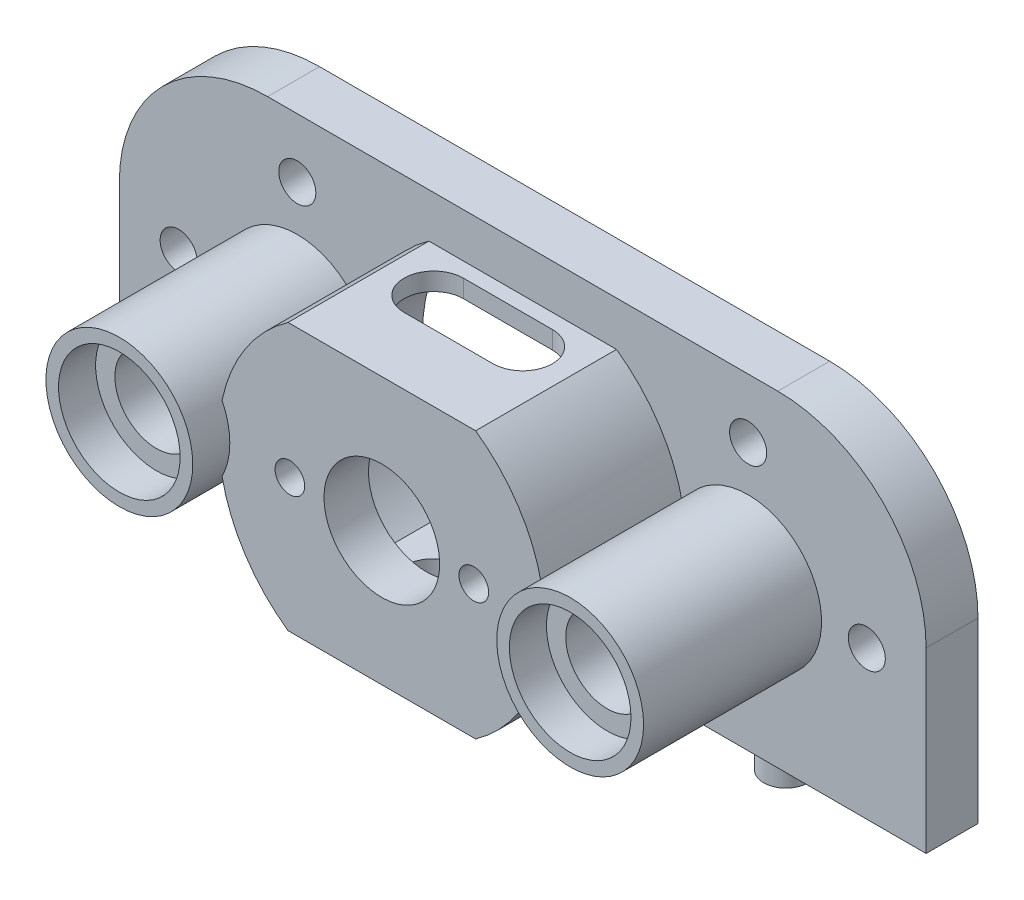
SolidWorks part; units mm, degrees
ref_plane "前视基准面" through (0, 0, 0) normal (0, 0, 1) x (1, 0, 0)
ref_plane "上视基准面" through (0, 0, 0) normal (0, 1, 0) x (1, 0, 0)
ref_plane "右视基准面" through (0, 0, 0) normal (1, 0, 0) x (0, 0, -1)
other "Configuration Table"
sketch "草图2" plane through (0, 0, 0) normal (0, 0, 1) x (1, 0, 0)
  line L0 (0, 0) -> (11.5094, 0) construction
  line L1 (0, 0) -> (0, 7.1412) construction
  line L2 (15.2, 0) -> (-15.2, 0) construction
  line L3 (15.2, -20) -> (-15.2, -20)
  line L4 (15.2, 20) -> (-15.2, 20)
  circle A0 centre (0, 0) radius 3.9
  circle A1 centre (-15.2, 0) radius 2.8
  circle A2 centre (-15.2, 0) radius 4.1
  arc A3 (15.2, -20) -> (15.2, 20) centre (15.2, 0) ccw
  arc A4 (-15.2, 20) -> (-15.2, -20) centre (-15.2, 0) ccw
  circle A5 centre (15.2, 0) radius 2.8
  circle A6 centre (15.2, 0) radius 4.1
  circle A7 centre (-6.2, 0) radius 1
  circle A9 centre (6.2, 0) radius 1
  circle A11 centre (-15.2, 8) radius 1.25
  circle A12 centre (-23.2, 0) radius 1.25
  circle A15 centre (23.2, 0) radius 1.25
  circle A16 centre (15.2, 8) radius 1.25
  point P11 (0, 0)
  dimension "D1" = 7.8
  dimension "D2" = 5.6
  dimension "D4" = 8.2
  dimension "D5" = 20
  dimension "D6" = 2
  dimension "D10" = 2.5
  dimension "D12" = 2.5
  dimension "D3" = 15.2
  dimension "D7" = 6.2
  dimension "D11" = 8
  dimension "D13" = 8
extrude "凸台-拉伸1" add sketch "草图2" along normal blind 3.5 contours L4 A4 L3 A3 A15 A6 A2 A0 A7 A9 A11 A12 A16 region at (0, -19.1903, 0)
extrude "凸台-拉伸2" add sketch "草图2<4>" along normal blind 1 contours A2 A1 | A6 A5 region at (-19.184, 0, 0) region at (11.216, 0, 0)
sketch "草图2<4>" plane through (0, 0, 0) normal (0, 0, 1) x (1, 0, 0) same geometry as "草图2"
sketch "草图3" plane through (0, 0, 3.5) normal (0, 0, 1) x (1, 0, 0)
  line L3 (15.2, -20) -> (-15.2, -20) construction
  line L4 (15.2, 20) -> (-15.2, 20) construction
  line L5 (15.2, -20) -> (-15.2, -20)
  line L6 (15.2, 20) -> (-15.2, 20)
  line L7 (-27.2, 12) -> (27.2, 12)
  line L8 (-27.2, 12) -> (-27.2, -10)
  line L9 (-27.2, -10) -> (27.2, -10)
  line L10 (27.2, 12) -> (27.2, -10)
  arc A2 (15.2, -20) -> (15.2, 20) centre (15.2, 0) ccw construction
  arc A3 (-15.2, 20) -> (-15.2, -20) centre (-15.2, 0) ccw construction
  arc A4 (15.2, -20) -> (15.2, 20) centre (15.2, 0) ccw
  arc A5 (-15.2, 20) -> (-15.2, -20) centre (-15.2, 0) ccw
  line M9 (15.2, 20) -> (-15.2, 20)
  arc M10 (-15.2, 20) -> (-15.2, -20) centre (-15.2, 0) ccw
  line M11 (-15.2, -20) -> (15.2, -20)
  arc M12 (15.2, -20) -> (15.2, 20) centre (15.2, 0) ccw
  dimension "D1" = 10
  dimension "D2" = 12
  dimension "D3" = 12
  dimension "D4" = 12
extrude "切除-拉伸1" cut sketch "草图3" against normal through all both and the other way through all contours M12 M9 M10 | M10 M11 M12 region at (0, -19.1903, 3.5)
fillet "圆角1" radius 10 2 edges at (-27.2, 12, 1.75) (27.2, 12, 1.75)
sketch "草图4" plane through (0, -10, 0) normal (0, -1, 0) x (1, 0, 0)
  line L0 (0, 0) -> (0, 12.3535) construction
  line L1 (-27.2, 3.5) -> (27.2, 3.5) construction
  line L2 (-27.2, 0) -> (-27.2, 3.5) construction
  line L3 (-12.4, 1) -> (-18, 1) construction
  line L4 (-12.4, 1) -> (-18, 1) construction
  circle A0 centre (-16, 1.75) radius 1.5
  circle A2 centre (-24, 1.75) radius 1
  circle A4 centre (16, 1.75) radius 1.5
  circle A5 centre (24, 1.75) radius 1
  point P26 (-15.2, 1)
  dimension "D1" = 3
  dimension "D6" = 2
  dimension "D8" = 27.2
  dimension "D2" = 1.75
  dimension "D3" = 16
  dimension "D7" = 24
  dimension "D9" = 0.8
extrude "切除-拉伸2" cut sketch "草图4" against normal blind 7 and the other way through all contours A2 | A5
extrude "凸台-拉伸3" add sketch "草图4<4>" along normal blind 1.6 contours A0 | A4 region at (-16, -10, 1.75) region at (16, -10, 1.75)
sketch "草图4<4>" plane through (0, -10, 0) normal (0, -1, 0) x (1, 0, 0) same geometry as "草图4"
sketch "草图5" plane through (0, 0, 0) normal (0, 0, -1) x (-1, 0, 0)
  line L0 (-6.3246, 9) -> (6.3246, 9)
  line L1 (-6.3246, -9) -> (6.3246, -9)
  line L5 (27.2, -10) -> (27.2, 2)
  line L6 (17.2, 12) -> (-17.2, 12)
  line L7 (-27.2, 2) -> (-27.2, -10)
  line L8 (-27.2, -10) -> (27.2, -10)
  line L9 (27.2, -10) -> (27.2, 2)
  line L10 (17.2, 12) -> (-17.2, 12)
  line L11 (-27.2, 2) -> (-27.2, -10)
  line L12 (-27.2, -10) -> (27.2, -10)
  circle A1 centre (0, 0) radius 11
  circle A2 centre (-6.2, 0) radius 1 construction
  circle A4 centre (6.2, 0) radius 1 construction
  circle A6 centre (0, 0) radius 3.9 construction
  circle A7 centre (-6.2, 0) radius 1
  circle A9 centre (6.2, 0) radius 1
  circle A11 centre (0, 0) radius 3.9
  arc A14 (27.2, 2) -> (17.2, 12) centre (17.2, 2) ccw
  arc A15 (-17.2, 12) -> (-27.2, 2) centre (-17.2, 2) ccw
  arc A16 (27.2, 2) -> (17.2, 12) centre (17.2, 2) ccw
  arc A17 (-17.2, 12) -> (-27.2, 2) centre (-17.2, 2) ccw
  circle M13 centre (-6.2, 0) radius 1
  circle M15 centre (6.2, 0) radius 1
  circle M16 centre (0, 0) radius 3.9
  dimension "D1" = 22
  dimension "D3" = 18
  dimension "D4" = 9
  dimension "D2" = 0
extrude "凸台-拉伸4" add sketch "草图5" against normal blind 13 contours L12 A1 M13 M15 M16 region at (0, 8.7157, 0)
sketch "草图6" plane through (0, 0, 0) normal (0, 0, -1) x (-1, 0, 0)
  line L0 (-6.65, 7.8) -> (6.65, 7.8)
  line L1 (6.65, -7.8) -> (-6.65, -7.8)
  circle A0 centre (0, 0) radius 10.25
  circle M17 centre (0, 0) radius 3.9
  circle M18 centre (6.2, 0) radius 1
  circle M20 centre (-6.2, 0) radius 1
  dimension "D1" = 20.5
  dimension "D3" = 15.6
extrude "切除-拉伸3" cut sketch "草图6" against normal offset from surface (10 mm away) 3 contours L0 A0 L1 M17 M20 M18 region at (0, 7.5424, 0) up to face at (-3.9, 0, 13)
sketch "草图7" plane through (0, 9, 0) normal (0, 1, 0) x (1, 0, 0)
  line L0 (-3, -6.5) -> (3, -6.5) construction
  line L1 (-3, -4.5) -> (3, -4.5)
  line L2 (-3, -8.5) -> (3, -8.5)
  line L3 (-17.2, -3.5) -> (17.2, -3.5) construction
  arc A0 (-3, -4.5) -> (-3, -8.5) centre (-3, -6.5) ccw
  arc A1 (3, -8.5) -> (3, -4.5) centre (3, -6.5) ccw
  point P2 (0, -6.5)
  dimension "D2" = 2
  dimension "D1" = 6
  dimension "D3" = 3
extrude "切除-拉伸4" cut sketch "草图7" against normal through all both and the other way through all
extrude "凸台-拉伸5" add sketch "草图2<5>" along normal blind 13 contours A2 A1 | A6 A5 region at (-19.184, 0, 0) region at (11.216, 0, 0)
sketch "草图2<5>" plane through (0, 0, 0) normal (0, 0, 1) x (1, 0, 0) same geometry as "草图2"
sketch "草图8" plane through (0, 0, 3.5) normal (0, 0, 1) x (1, 0, 0)
  line L0 (0, 0) -> (0, -7.8) construction
  arc A0 (-6.65, 7.8) -> (-6.65, -7.8) centre (0, 0) ccw construction
  arc A1 (-6.65, 7.8) -> (-6.65, -7.8) centre (0, 0) ccw
  circle A2 centre (-15.2, 0) radius 4.95
  circle A3 centre (15.2, 0) radius 4.95
  circle M3 centre (-15.2, 0) radius 4.1
  circle M4 centre (15.2, 0) radius 4.1
  arc M14 (-6.3246, -9) -> (-6.3246, 9) centre (0, 0) cw
  arc M16 (6.3246, 9) -> (6.3246, -9) centre (0, 0) cw
extrude "凸台-拉伸6" add sketch "草图8" along normal blind 12 contours A2 M14 M3 | A3 M16 M4 region at (-11.0136, 0, 3.5) region at (16.3077, -4.6845, 3.5)
extrude "凸台-拉伸7" add sketch "草图8<4>" along normal up to surface (12 mm away) from surface contours A2 M14 | A3 M16 region at (-10.6536, 0, 3.5) region at (10.6536, 0, 3.5) up to face at (15.575, 0, 15.5) starting at face at (-3.9, 0, 13)
sketch "草图8<4>" plane through (0, 0, 3.5) normal (0, 0, 1) x (1, 0, 0) same geometry as "草图8"
extrude "切除-拉伸10" cut sketch "草图2<6>" along normal blind 2.5 contours A2 A1 | A6 A5 region at (-19.184, 0, 0) region at (11.216, 0, 0)
sketch "草图2<6>" plane through (0, 0, 0) normal (0, 0, 1) x (1, 0, 0) same geometry as "草图2"
